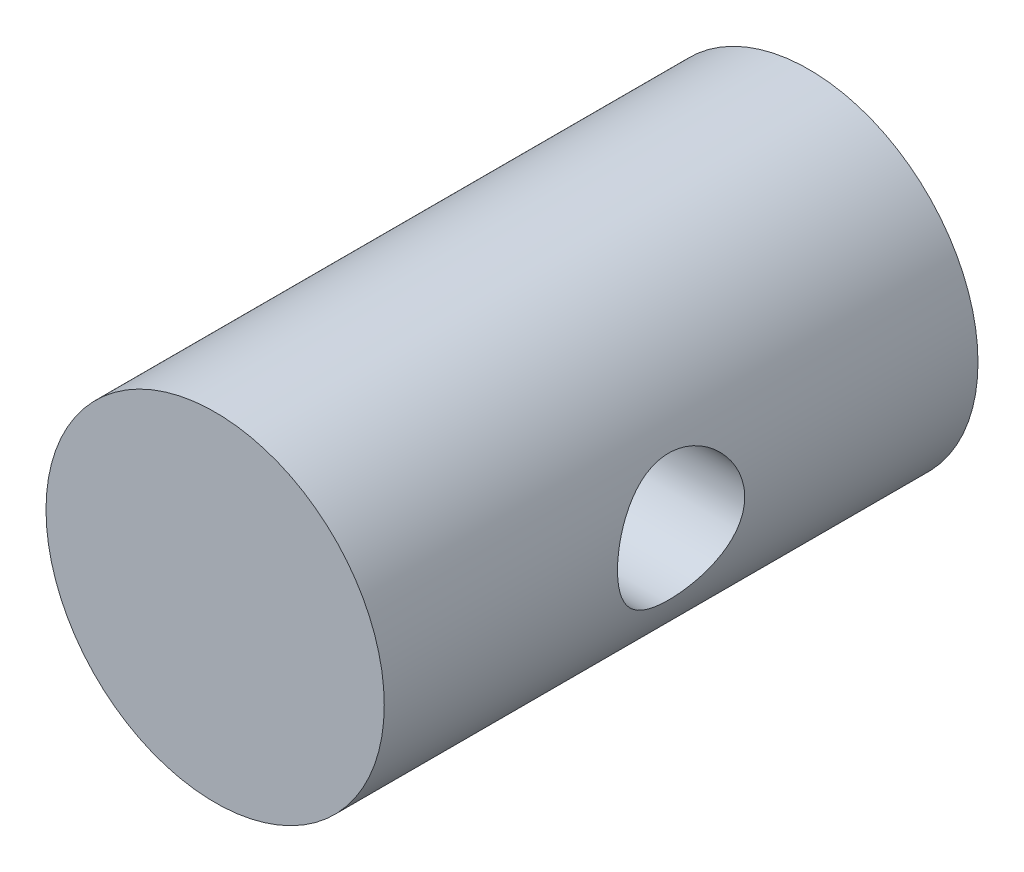
SolidWorks part; units mm, degrees
ref_plane "Front Plane" through (0, 0, 0) normal (1, 0, 0) x (0, 1, 0)
ref_plane "Top Plane" through (0, 0, 0) normal (0, 0, 1) x (0, 1, 0)
ref_plane "Right Plane" through (0, 0, 0) normal (0, 1, 0) x (-1, 0, 0)
sketch "Sketch1" plane through (0, 0, 0) normal (0, 0, 1) x (0, 1, 0)
  circle A0 centre (0, 0) radius 12.6619
  dimension "D1" = 25.3238
extrude "Boss-Extrude1" add sketch "Sketch1" along normal blind 44.45
sketch "Sketch2" plane through (0, 0, 0) normal (1, 0, 0) x (0, 1, 0)
  line L0 (0, 0) -> (0, 22.225) construction
  line L1 (0, 22.225) -> (0, 44.45) construction
  line L2 (12.6619, 44.45) -> (-12.6619, 44.45) construction
  circle A0 centre (0, 22.225) radius 4.7625
  dimension "D1" = 9.525
extrude "Cut-Extrude1" cut sketch "Sketch2" against normal through all both and the other way through all
